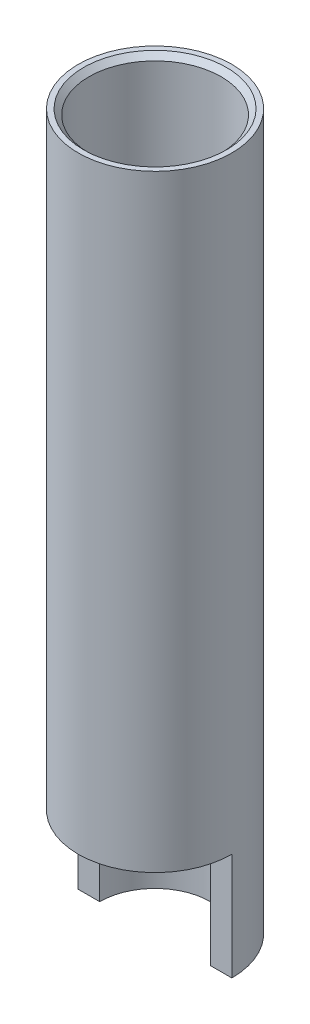
SolidWorks part; units mm, degrees
material "Copper"
ref_plane "Plano frontal" through (0, 0, 0) normal (0, 0, 1) x (1, 0, 0)
ref_plane "Plano superior" through (0, 0, 0) normal (0, 1, 0) x (1, 0, 0)
ref_plane "Plano direito" through (0, 0, 0) normal (1, 0, 0) x (0, 0, -1)
sketch "Esboço1" plane through (0, 0, 0) normal (0, 0, 1) x (1, 0, 0)
  line L0 (0, 4) -> (0, 10)
  line L1 (0, 0) -> (2.15, 0) construction
  line L2 (2.15, 0) -> (2.15, 20)
  line L3 (2.15, 20) -> (1.85, 20)
  line L4 (1.55, 0) -> (1.55, 3)
  line L5 (1.55, 0) -> (2.15, 0)
  line L6 (1.55, 3) -> (0, 4)
  line L7 (1.85, 20) -> (1.85, 11)
  line L8 (1.85, 11) -> (0, 10)
  dimension "D1" = 0.3
  dimension "D2" = 2.15
  dimension "D3" = 0.6
  dimension "D4" = 4
  dimension "D5" = 1
  dimension "D6" = 10
  dimension "D7" = 20
  dimension "D8" = 1
revolve "Revolução1" add sketch "Esboço1" angle 360 about L0
sketch "Esboço3" plane through (0, 0, 0) normal (0, -1, 0) x (1, 0, 0)
  line L1 (-2.3943, 2.452) -> (2.3943, 2.452)
  line L2 (-2.3943, 2.452) -> (-2.3943, 0)
  line L3 (-2.3943, 0) -> (2.3943, 0)
  line L4 (2.3943, 2.452) -> (2.3943, 0)
extrude "Corte-extrusão4" cut sketch "Esboço3" against normal blind 3
other "PontoC1" parameters "Diâmetro"=5, "ComprimentoAdaptador"=0
ref_axis "Eixo1" through (0, -7, 0) along (0, 1, 0)
chamfer "Chanfro1" distance 0.15 angle 45 1 edges at (0, 20, -1.85)
